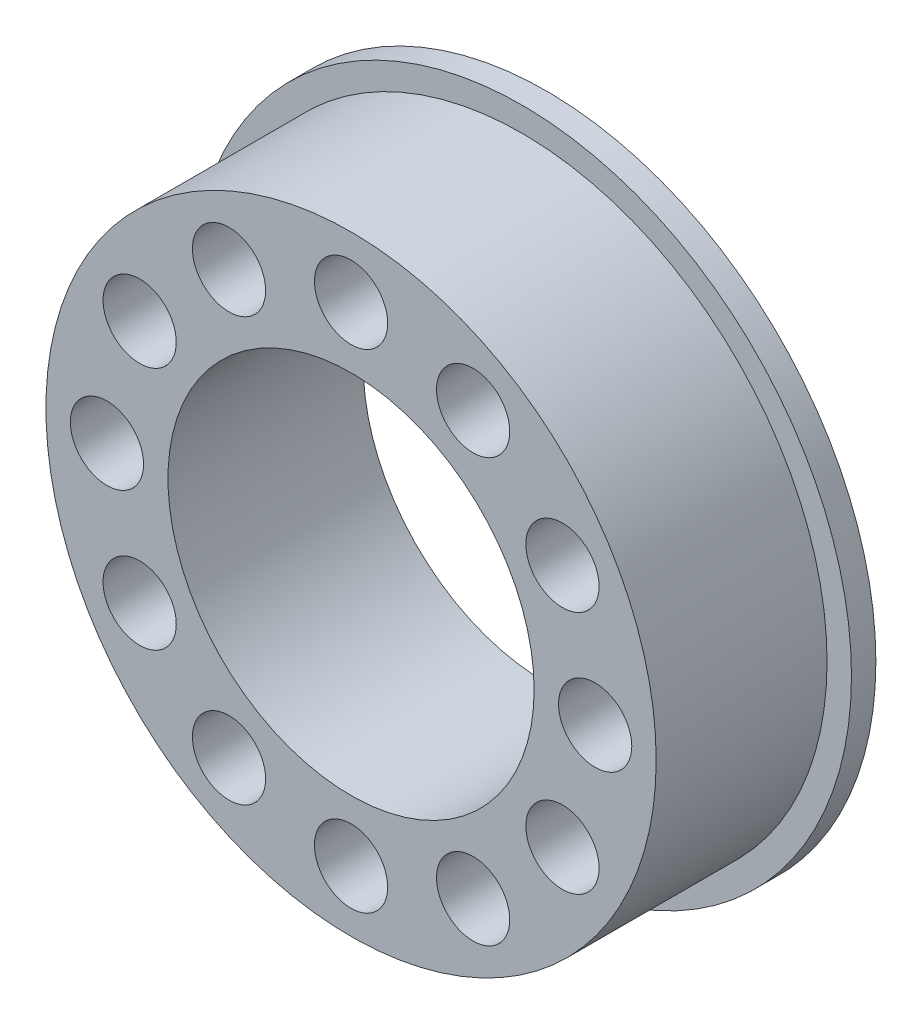
SolidWorks part; units mm, degrees
material "A2017"
ref_plane "正面" through (0, 0, 0) normal (0, 0, 1) x (1, 0, 0)
ref_plane "平面" through (0, 0, 0) normal (0, 1, 0) x (1, 0, 0)
ref_plane "右側面" through (0, 0, 0) normal (1, 0, 0) x (0, 0, -1)
sketch "ｽｹｯﾁ1" plane through (0, 0, 0) normal (1, 0, 0) x (0, 0, -1)
  line L0 (0, 0) -> (14.0759, 0) construction
  line L1 (0, 7.5) -> (8, 7.5)
  line L2 (8, 7.5) -> (8, 13.5)
  line L3 (8, 13.5) -> (7, 13.5)
  line L4 (7, 13.5) -> (7, 12.5)
  line L5 (7, 12.5) -> (0, 12.5)
  line L6 (0, 12.5) -> (0, 7.5)
  dimension "D1" = 25
  dimension "D2" = 15
  dimension "D3" = 8
  dimension "D4" = 1
  dimension "D5" = 27
revolve "回転1" add sketch "ｽｹｯﾁ1" angle 360 about L0
sketch "ｽｹｯﾁ2" plane through (0, 0, 0) normal (0, 0, 1) x (1, 0, 0)
  circle A0 centre (0, 0) radius 10 construction
  circle A1 centre (0, 10) radius 1.5
  circle A2 centre (5, 8.6603) radius 1.5
  circle A3 centre (8.6603, 5) radius 1.5
  circle A4 centre (10, 0) radius 1.5
  circle A5 centre (8.6603, -5) radius 1.5
  circle A6 centre (5, -8.6603) radius 1.5
  circle A7 centre (0, -10) radius 1.5
  circle A8 centre (-5, -8.6603) radius 1.5
  circle A9 centre (-8.6603, -5) radius 1.5
  circle A10 centre (-10, 0) radius 1.5
  circle A11 centre (-8.6603, 5) radius 1.5
  circle A12 centre (-5, 8.6603) radius 1.5
  point P29 (0, 0)
  dimension "D1" = 3
  dimension "D2" = 20
  dimension "D3" = 12
extrude "ｶｯﾄ - 押し出し1" cut sketch "ｽｹｯﾁ2" against normal through all
